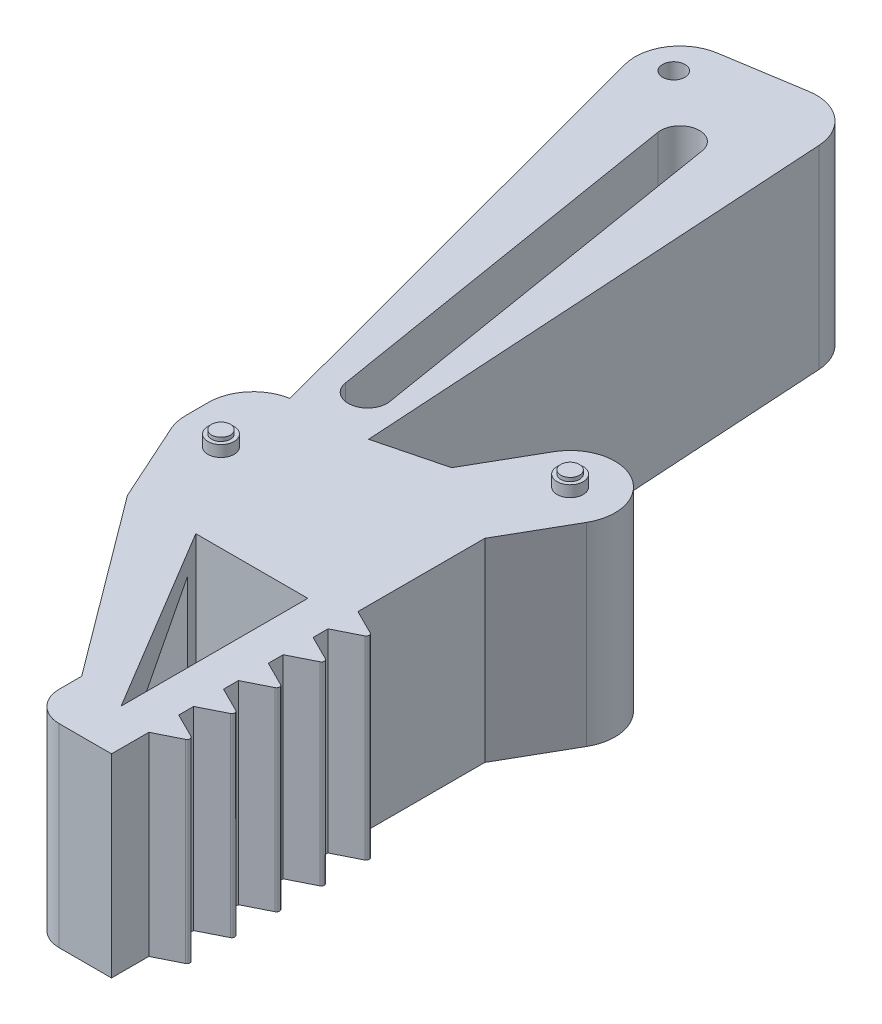
SolidWorks part; units mm, degrees
material "Cast Alloy Steel"
ref_plane "Front Plane" through (0, 0, 0) normal (0, 0, 1) x (1, 0, 0)
ref_plane "Top Plane" through (0, 0, 0) normal (0, 1, 0) x (1, 0, 0)
ref_plane "Right Plane" through (0, 0, 0) normal (1, 0, 0) x (0, 0, -1)
sketch "Sketch1" plane through (0, 0, 0) normal (0, 1, 0) x (1, 0, 0)
  line L0 (-8.5023, -32.8801) -> (-26.5375, 34.7566)
  line L1 (-26.5375, 34.7566) -> (-2.8341, 38.5181)
  line L2 (-2.8341, 38.5181) -> (1.4977, -32.3496)
  line L4 (1.4977, -32.3496) -> (-13.5023, -33.1454)
  line L5 (-13.5023, -33.1454) -> (-13.5023, -43.1454)
  line L6 (-13.5023, -43.1454) -> (-8.1519, -54.9933)
  line L7 (-8.1519, -54.9933) -> (9.7696, -79.052)
  line L13 (9.7696, -79.052) -> (9.7696, -86.052)
  line L14 (9.7696, -86.052) -> (20.7696, -86.052)
  line L15 (20.7696, -86.052) -> (20.7696, -36.052)
  line L16 (20.7696, -36.052) -> (25.742, -27.3758)
  line L17 (1.4977, -32.3496) -> (10.3582, -30.0851)
  line L18 (10.3582, -30.0851) -> (15.3306, -21.409)
  arc A0 (25.742, -27.3758) -> (15.3306, -21.409) centre (20.5363, -24.3924) ccw
  dimension "D1" = 70
  dimension "D2" = 24
  dimension "D3" = 71
  dimension "D4" = 15
  dimension "D5" = 10
  dimension "D6" = 38.5181
  dimension "D7" = 34.7566
  dimension "D8" = 10
  dimension "D9" = 13
  dimension "D10" = 30
  dimension "D11" = 7
  dimension "D12" = 11
  dimension "D13" = 50
  dimension "D14" = 10
  dimension "D15" = 12
  dimension "D16" = 32.8801
  dimension "D17" = 9.1453
  dimension "D18" = 30.0851
extrude "Boss-Extrude1" add sketch "Sketch1" along normal mid plane 26 contours L4 L2 L1 L0 | L16 A0 L18 L17 L4 L5 L6 L7 L13 L14 L15 region at (-9.8353, 0, -6.7884) region at (8.5305, 0, 50.5291)
sketch "Sketch2" plane through (0, 13, 0) normal (0, 1, 0) x (1, 0, 0)
  line L0 (0.8787, -54.8713) -> (15.8787, -54.8713)
  line L1 (15.8787, -54.8713) -> (15.8787, -79.8713)
  line L2 (0.8787, -54.8713) -> (15.8787, -79.8713)
  dimension "D1" = 15
  dimension "D2" = 25
extrude "Cut-Extrude1" cut sketch "Sketch2" against normal blind 26
sketch "Sketch3" plane through (0, 13, 0) normal (0, 1, 0) x (1, 0, 0)
  line L0 (20.7696, -86.052) -> (20.7696, -36.052) construction
  line L1 (9.7696, -86.052) -> (20.7696, -86.052) construction
  line L2 (20.7696, -86.052) -> (20.7696, -81.052)
  line L3 (20.7696, -81.052) -> (20.7696, -77.052)
  line L4 (20.7696, -79.052) -> (24.7696, -79.052)
  line L5 (20.7696, -77.052) -> (24.7696, -79.052)
  line L6 (20.7696, -81.052) -> (24.7696, -79.052)
  point P0 (20.7696, -81.052)
  line M13 (20.7696, -86.052) -> (20.7696, -36.052)
  dimension "D1" = 5
  dimension "D2" = 4
  dimension "D3" = 4
extrude "Boss-Extrude3" add sketch "Sketch3" against normal blind 26 contours L5 L3 L4 | L6 L4 M13 region at (22.1029, 13, 79.7187) region at (22.1029, 13, 78.3853)
pattern_linear "LPattern1" count 5 spacing 6 along (0, 0, -1) of "Boss-Extrude3"
fillet "Fillet1" radius 6 2 edges at (-2.8341, 0, -38.5181) (-26.5375, 0, -34.7566)
fillet "Fillet2" radius 0.4 1 edges at (24.7696, 0, 79.052)
fillet "Fillet3" radius 0.4 1 edges at (24.7696, 0, 73.052)
fillet "Fillet4" radius 0.4 1 edges at (24.7696, 0, 67.052)
fillet "Fillet5" radius 0.4 1 edges at (24.7696, 0, 61.052)
fillet "Fillet6" radius 0.4 1 edges at (24.7696, 0, 55.052)
fillet "Fillet7" radius 6 2 edges at (-13.5023, 0, 43.1454) (-13.5023, 0, 33.1454)
fillet "Fillet8" radius 4 1 edges at (9.7696, 0, 86.052)
sketch "Sketch4" plane through (0, 13, 0) normal (0, 1, 0) x (1, 0, 0)
  circle A0 centre (-20.7989, 30.8176) radius 1.5
  dimension "D1" = 3
extrude "Cut-Extrude2" cut sketch "Sketch4" against normal up to surface (26 mm away) up to face at (10.8787, -13, 63.2046)
sketch "Sketch5" plane through (-31.5887, 0, 23.5307) normal (-0.802, 0, 0.5974) x (0.5974, 0, 0.802)
  line L0 (46.2324, 10.5) -> (46.2324, -10)
  line L1 (39.2324, 13) -> (69.2324, 13) construction
  line L2 (39.2324, -13) -> (69.2324, -13) construction
  line L3 (39.2324, 13) -> (39.2324, -13) construction
  line L4 (46.2324, -10) -> (67.2324, -4.6147)
  line L5 (46.2324, 10.5) -> (67.2324, 7.3853)
  line L6 (67.2324, 9.0061) -> (67.2324, -9.3292)
  line L7 (69.2324, 13) -> (69.2324, -13) construction
  dimension "D1" = 2.5
  dimension "D2" = 3
  dimension "D3" = 7
  dimension "D4" = 2
  dimension "D5" = 12
  dimension "D6" = 104.383
extrude "Cut-Extrude3" cut sketch "Sketch5" against normal blind 7 contours L6 L5 L0 L4 region at (1.7555, 0.7682, 68.2935)
sketch "Sketch6" plane through (0, 13, 0) normal (0, 1, 0) x (1, 0, 0)
  circle A0 centre (20.5363, -24.3924) radius 1.75
  circle A1 centre (-7.5023, -43.1164) radius 1.75
  dimension "D1" = 3.5
  dimension "D2" = 3.5
extrude "Boss-Extrude4" add sketch "Sketch6" along normal blind 1.5
sketch "Sketch7" plane through (0, 14.5, 0) normal (0, 1, 0) x (1, 0, 0)
  circle A0 centre (-7.5023, -43.1164) radius 1.25
  circle A1 centre (-7.5023, -43.1164) radius 1.75 construction
  circle A2 centre (20.5363, -24.3924) radius 1.25
  circle A3 centre (20.5363, -24.3924) radius 1.75 construction
  dimension "D1" = 0.5
  dimension "D2" = 0.5
extrude "Boss-Extrude5" add sketch "Sketch7" along normal blind 0.5
sketch "Sketch8" plane through (0, 15, 0) normal (0, 1, 0) x (1, 0, 0)
  line L0 (-12.1755, 23.034) -> (-4.0206, -26.966) construction
  line L1 (-9.6141, 23.4517) -> (-1.4593, -26.5483)
  line L2 (-14.7368, 22.6162) -> (-6.582, -27.3838)
  arc A0 (-9.6141, 23.4517) -> (-14.7368, 22.6162) centre (-12.1755, 23.034) ccw
  arc A1 (-6.582, -27.3838) -> (-1.4593, -26.5483) centre (-4.0206, -26.966) ccw
  point P2 (-8.098, -1.966)
  dimension "D1" = 50
extrude "Cut-Extrude7" cut sketch "Sketch8" against normal blind 10
mirror "Mirror1" about plane through (0, 0, 0) normal (0, 1, 0) of "Boss-Extrude4", "Boss-Extrude5", "Cut-Extrude7"
